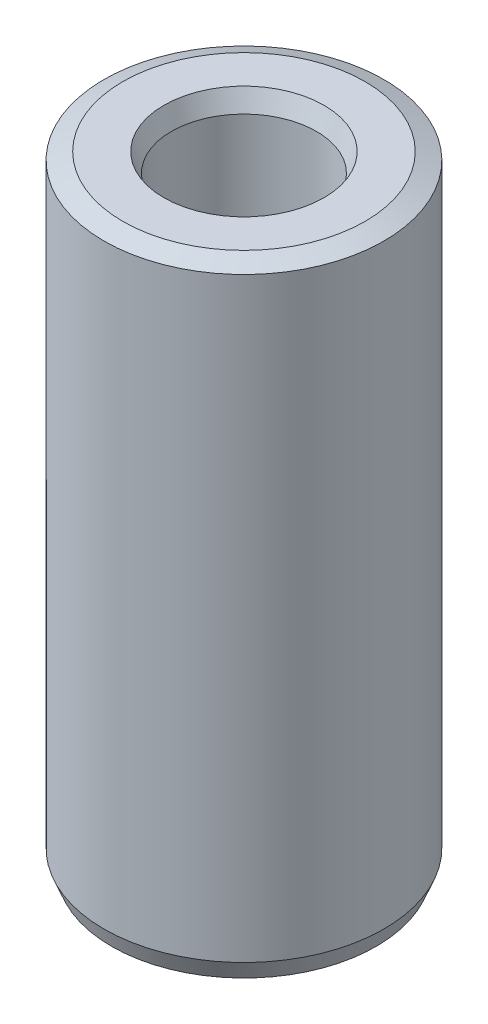
SolidWorks part; units mm, degrees
ref_plane "Front Plane" through (0, 0, 0) normal (0, 0, 1) x (1, 0, 0)
ref_plane "Top Plane" through (0, 0, 0) normal (0, 1, 0) x (1, 0, 0)
ref_plane "Right Plane" through (0, 0, 0) normal (1, 0, 0) x (0, 0, -1)
sketch "Sketch1" plane through (0, 0, 0) normal (0, 1, 0) x (1, 0, 0)
  circle A0 centre (0, 0) radius 32.5
  dimension "SLEEVE_OD" = 65
extrude "Boss-Extrude1" add sketch "Sketch1" along normal blind 144.5087
sketch "Sketch2" plane through (0, 0, 0) normal (0, 1, 0) x (1, 0, 0)
  circle A0 centre (0, 0) radius 16.8374
  dimension "BORE_D" = 33.6747
extrude "Cut-Extrude1" cut sketch "Sketch2" along normal through all
chamfer "Chamfer1" distance 1.7622 angle 68.037 4 edges at (0, 144.5087, 16.8374) (0, 0, 16.8374) (0, 0, 32.5) (0, 144.5087, 32.5) first distance on face at (0, 144.5087, 16.8374) first distance on face at (0, 0, 16.8374) first distance on face at (0, 144.5087, 32.5)
